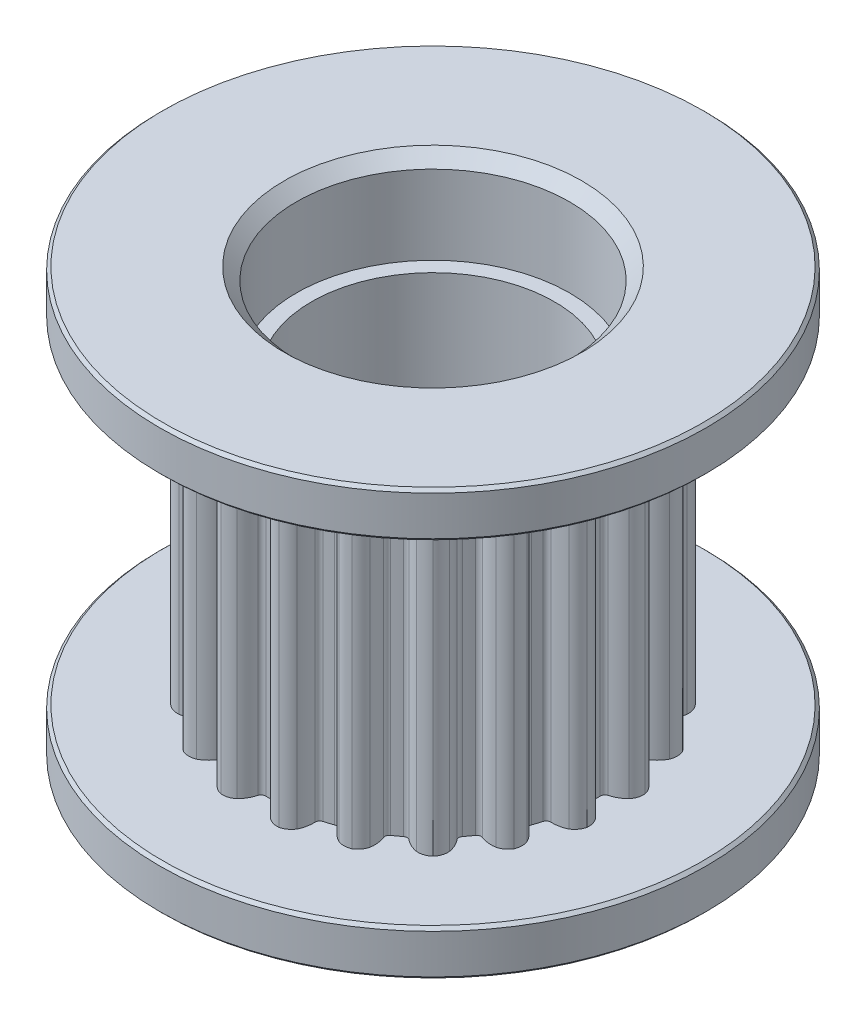
SolidWorks part; units mm, degrees
material "6061 Alloy"
ref_plane "Front Plane" through (0, 0, 0) normal (0, 0, 1) x (1, 0, 0)
ref_plane "Top Plane" through (0, 0, 0) normal (0, 1, 0) x (1, 0, 0)
ref_plane "Right Plane" through (0, 0, 0) normal (1, 0, 0) x (0, 0, -1)
sketch "BodyS" plane through (0, 0, 0) normal (0, 0, 1) x (1, 0, 0)
  line L0 (6.11, -5.5) -> (6.11, 5.5)
  line L1 (6.11, 5.5) -> (9, 5.5)
  line L2 (9, 5.5) -> (9, 7)
  line L3 (9, 7) -> (4.5, 7)
  line L4 (4.5, 7) -> (4.5, 4)
  line L5 (4.5, 4) -> (4, 4)
  line L6 (4, 4) -> (4, -4)
  line L7 (4, -4) -> (4.5, -4)
  line L8 (4.5, -4) -> (4.5, -7)
  line L9 (4.5, -7) -> (9, -7)
  line L10 (9, -7) -> (9, -5.5)
  line L11 (9, -5.5) -> (6.11, -5.5)
  line L12 (0, 0) -> (4, 0) construction
  line L13 (0, 7) -> (0, -7) construction
  dimension "BearingOD" = 9
  dimension "Height" = 14
  dimension "FlangeHeight" = 1.5
  dimension "BearingHeight" = 3
  dimension "BearingRestDiaControl" = 0.5
  dimension "RefBodyInnerDiameter" = 8
  dimension "FlangeDiaControl" = 4.5
  dimension "RefFlangeDia" = 18
  dimension "BeltPathDiaControl" = 1.61
  dimension "RefBeltPathDia" = 12.22
revolve "Body" add sketch "BodyS" angle 360 about L13
sketch "GT2ProfileS" plane through (0, 0, 0) normal (0, 1, 0) x (1, 0, 0)
  line L1 (0, -6.11) -> (0, -5.36) construction
  line L2 (-0.9955, -6.0283) -> (-0.8733, -5.2884) construction
  line L3 (0, 0) -> (-0.8733, -5.2884) construction
  line L4 (0.9955, -6.0283) -> (0, 0) construction
  arc A3 (0.2997, -5.4688) -> (0.1507, -5.3579) centre (0.1549, -5.5078) ccw
  arc A4 (-0.9955, -6.0283) -> (0.9955, -6.0283) centre (0, 0) ccw
  arc A5 (-0.2997, -5.4688) -> (-0.1507, -5.3579) centre (-0.1549, -5.5078) cw
  arc A6 (-0.2997, -5.4688) -> (-0.5497, -5.907) centre (-1.2653, -5.2085) cw
  circle A7 centre (0, 0) radius 6.11 construction
  arc A8 (-0.1507, -5.3579) -> (0.1507, -5.3579) centre (0, 0) ccw
  arc A9 (-0.5497, -5.907) -> (-0.9955, -6.0283) centre (-0.9051, -5.4808) cw
  arc A10 (0.2997, -5.4688) -> (0.5497, -5.907) centre (1.2653, -5.2085) ccw
  arc A11 (0.5497, -5.907) -> (0.9955, -6.0283) centre (0.9051, -5.4808) ccw
  circle A12 centre (0, 0) radius 5.36 construction
  dimension "BottomRadius" = 0.15
  dimension "MidRadius" = 1
  dimension "TopRadius" = 0.555
  dimension "Height" = 0.75
  dimension "XDistMidRadius" = 0.4
  dimension "ArcLengthAngle" = 18.755
  dimension "ArcLength" = 2
sketch "ThruBoreS" [suppressed] plane through (0, 0, 0) normal (0, 1, 0) x (1, 0, 0)
  circle A0 centre (0, 0) radius 4
  circle A2 centre (0, 0) radius 4 construction
extrude "ThruBore" [suppressed] cut sketch "ThruBoreS" against normal through all both and the other way through all
extrude "GT2Profile" cut sketch "GT2ProfileS" against normal up to surface and the other way up to surface up to face at (0, -5.5, 6.11) other way up to face at (0, 5.5, 9)
pattern_circular "GT2 Groove CP" count 20 over 360 about axis through (0, 7, 0) along (0, 1, 0) of "GT2Profile"
chamfer "InnerC" distance 0.4 angle 45 2 edges at (0, -7, 4.5) (0, 7, 4.5)
chamfer "OuterC" distance 0.1 angle 45 4 edges at (0, -7, 9) (0, -5.5, 9) (0, 5.5, 9) (0, 7, 9)
equation "\"NumTeeth@GT2 Groove CP\"=int(360/\"ArcLengthAngle@GT2ProfileS\")+1"
